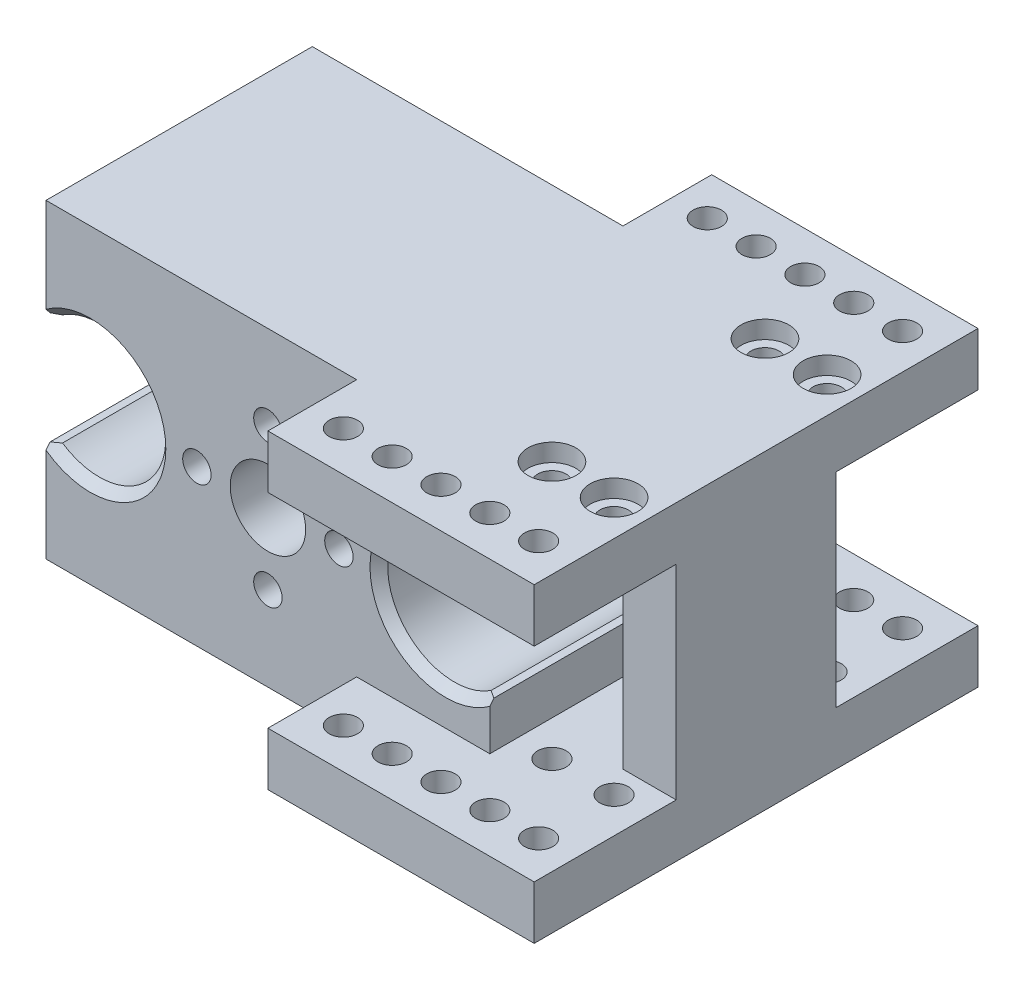
SolidWorks part; units mm, degrees
ref_plane "前视基准面" through (0, 0, 0) normal (0, 0, 1) x (1, 0, 0)
ref_plane "上视基准面" through (0, 0, 0) normal (0, 1, 0) x (1, 0, 0)
ref_plane "右视基准面" through (0, 0, 0) normal (1, 0, 0) x (0, 0, -1)
other "Configuration Table"
sketch "草图1" plane through (0, 0, 0) normal (0, 0, 1) x (1, 0, 0)
  line L1 (-25, -17.5) -> (25, -17.5)
  line L2 (-25, -17.5) -> (-25, 17.5)
  line L3 (-25, 17.5) -> (25, 17.5)
  line L4 (25, -17.5) -> (25, 17.5)
  line L5 (-25, -17.5) -> (25, 17.5) construction
  line L6 (-25, 17.5) -> (25, -17.5) construction
  point P0 (0, 0)
  dimension "D1" = 50
  dimension "D2" = 35
extrude "凸台-拉伸1" add sketch "草图1" along normal blind 30
hole_wizard "光轴孔" positions "草图2" profile "草图3" legacy end condition through all
sketch "草图2" plane through (0, 0, 30) normal (0, 0, 1) x (1, 0, 0)
  point P0 (0, 0)
sketch "草图3" plane through (0, 0, 30) normal (1, 0, 0) x (0, -1, 0)
  line L0 (0, 0) -> (0, 30)
  line L1 (0, 30) -> (4.25, 30)
  line L2 (4.25, 30) -> (4.25, 0)
  line L3 (4.25, 0) -> (0, 0)
  line L4 (0, 110) -> (0, -10) construction
  dimension "直径" = 8.5
  dimension "深度" = 30
hole_wizard "光轴座螺丝孔" positions "草图4" profile "草图5" legacy end condition through all
sketch "草图4" plane through (0, 0, 30) normal (0, 0, 1) x (1, 0, 0)
  point P0 (8, 0)
  point P4 (0, 8)
  point P6 (-8, 0)
  point P8 (0, -8)
  dimension "D1" = 8
  dimension "D2" = 8
  dimension "D3" = 8
  dimension "D4" = 8
sketch "草图5" plane through (8, 0, 30) normal (1, 0, 0) x (0, -1, 0)
  line L0 (0, 0) -> (0, 30)
  line L1 (0, 30) -> (1.6, 30)
  line L2 (1.6, 30) -> (1.6, 0)
  line L3 (1.6, 0) -> (0, 0)
  line L4 (0, 110) -> (0, -10) construction
  dimension "直径" = 3.2
  dimension "深度" = 30
hole_wizard "直线轴承座孔" positions "草图6" profile "草图7" legacy end condition through all
sketch "草图6" plane through (0, 0, 30) normal (0, 0, 1) x (1, 0, 0)
  point P0 (20, 0)
  point P2 (-20, 0)
  dimension "D1" = 20
  dimension "D2" = 20
sketch "草图7" plane through (20, 0, 30) normal (1, 0, 0) x (0, -1, 0)
  line L0 (0, 0) -> (0, 30)
  line L1 (0, 30) -> (7.5, 30)
  line L2 (7.5, 30) -> (7.5, 0)
  line L3 (7.5, 0) -> (0, 0)
  line L4 (0, 110) -> (0, -10) construction
  dimension "直径" = 15
  dimension "深度" = 30
chamfer "倒角1" distance 1 angle 45 8 edges at (25, -5.5902, 15) (12.5, 0, 30) (25, 5.5902, 15) (12.5, 0, 0) (-12.5, 0, 30) (-12.5, 0, 0) (-25, 5.5902, 15) (-25, -5.5902, 15) first distance on face at (18.75, 0, 15) first distance on face at (-18.75, 0, 15)
sketch "草图9" plane through (25, 0, 0) normal (1, 0, 0) x (0, 0, -1)
  line L0 (0, 6.8739) -> (0, 17.5) construction
  line L1 (-30, 17.5) -> (0, 17.5)
  line L2 (-30, 17.5) -> (-30, 11.5)
  line L3 (-30, 11.5) -> (0, 11.5)
  line L4 (0, 17.5) -> (0, 11.5)
  line L5 (-30, -17.5) -> (-30, -6.8739) construction
  line L6 (0, -17.5) -> (-30, -17.5)
  line L7 (0, -17.5) -> (0, -11.5)
  line L8 (0, -11.5) -> (-30, -11.5)
  line L9 (-30, -17.5) -> (-30, -11.5)
  dimension "D1" = 6
  dimension "D2" = 6
extrude "凸台-拉伸3" add sketch "草图9" along normal blind 15
ref_plane "基准面1" through (0, 0, 15) normal (0, 0, 1) x (1, 0, 0)
sketch "草图10" plane through (0, 0, 15) normal (0, 0, 1) x (1, 0, 0)
  line L6 (40, 11.5) -> (25, 11.5) construction
  line L7 (40, -11.5) -> (34, -11.5)
  line L8 (40, -11.5) -> (40, 11.5)
  line L9 (40, 11.5) -> (34, 11.5)
  line L10 (34, -11.5) -> (34, 11.5)
  dimension "D1" = 6
extrude "凸台-拉伸4" add sketch "草图10" along normal mid plane 18
hole_wizard "孔1" positions "草图11" profile "草图12" legacy end condition through all
sketch "草图11" plane through (0, 11.5, 0) normal (0, -1, 0) x (-1, 0, 0)
  line L0 (-40, 0) -> (-25, 0) construction
  line L3 (-40, -6) -> (-40, 0) construction
  line L4 (-25, -30) -> (-25, 0) construction
  point P0 (-36, -3)
  point P27 (-29, -3)
  dimension "D1" = 3
  dimension "D2" = 4
  dimension "D3" = 4
sketch "草图12" plane through (36, 11.5, 3) normal (1, 0, 0) x (0, 0, -1)
  line L0 (0, 0) -> (0, 6)
  line L1 (0, 6) -> (1.6, 6)
  line L2 (1.6, 6) -> (1.6, 0)
  line L3 (1.6, 0) -> (0, 0)
  line L4 (0, 110) -> (0, -10) construction
  dimension "直径" = 3.2
  dimension "深度" = 6
mirror "镜向1" about plane through (0, 0, 15) normal (0, 0, 1) of "孔1"
ref_plane "基准面2" through (0, 0, 0) normal (0, -1, 0) x (-1, 0, 0)
mirror "镜向2" about plane through (0, 0, 0) normal (0, -1, 0) of "镜向1", "孔1"
sketch "草图15" plane through (0, 0, 0) normal (0, 0, -1) x (-1, 0, 0)
  line L0 (-40, 17.5) -> (25, 17.5) construction
  line L1 (-40, 11.5) -> (-10, 11.5)
  line L2 (-40, 11.5) -> (-40, 17.5)
  line L3 (-40, 17.5) -> (-10, 17.5)
  line L4 (-10, 11.5) -> (-10, 17.5)
  dimension "D1" = 30
extrude "凸台-拉伸6" add sketch "草图15" along normal blind 10
hole_wizard "孔2" positions "草图16" profile "草图17" legacy end condition through all
sketch "草图16" plane through (0, 11.5, 0) normal (0, -1, 0) x (-1, 0, 0)
  line L0 (-40, 10) -> (-10, 10) construction
  line L1 (-10, 10) -> (-10, 0) construction
  line L4 (-14, 5.5) -> (-25, 5.5)
  line L5 (-25, 10) -> (-25, 0)
  line L6 (-10, 10) -> (-40, 10) construction
  point P6 (-19.5, 5.5)
  point P8 (-14, 5.5)
  point P10 (-25, 5.5)
  dimension "D1" = 4.5
  dimension "D2" = 4
sketch "草图17" plane through (19.5, 11.5, -5.5) normal (1, 0, 0) x (0, 0, -1)
  line L0 (0, 0) -> (0, 6)
  line L1 (0, 6) -> (1.6, 6)
  line L2 (1.6, 6) -> (1.6, 0)
  line L3 (1.6, 0) -> (0, 0)
  line L4 (0, 110) -> (0, -10) construction
  dimension "直径" = 3.2
  dimension "深度" = 6
ref_plane "基准面3" through (25, 0, 0) normal (1, 0, 0) x (0, 0, -1)
mirror "镜向4" about plane through (25, 0, 0) normal (1, 0, 0) of "孔2"
mirror "镜向5" about plane through (0, 0, 15) normal (0, 0, 1) of "镜向4", "孔2", "凸台-拉伸6"
mirror "镜向6" about plane through (0, 0, 0) normal (0, -1, 0) of "镜向5", "镜向4", "孔2", "凸台-拉伸6"
hole_wizard "孔3" positions "草图19" profile "草图20" legacy
sketch "草图19" plane through (0, -17.5, 0) normal (0, -1, 0) x (-1, 0, 0)
  point P0 (-29, -3)
  point P3 (-36, -3)
  point P6 (-36, -27)
  point P9 (-29, -27)
sketch "草图20" plane through (29, -17.5, 3) normal (1, 0, 0) x (0, 0, -1)
  line L0 (0, 0) -> (0, 2)
  line L1 (0, 2) -> (2.7, 2)
  line L2 (2.7, 2) -> (2.7, 0)
  line L3 (2.7, 0) -> (0, 0)
  line L4 (0, 110) -> (0, -10) construction
  dimension "直径" = 5.4
  dimension "深度" = 2
mirror "镜向7" about plane through (0, 0, 0) normal (0, -1, 0) of "孔3"
hole_wizard "孔4" positions "草图21" profile "草图22" legacy
sketch "草图21" plane through (0, 0, 0) normal (0, 0, -1) x (-1, 0, 0)
  point P0 (0, 0)
sketch "草图22" plane through (0, 0, 0) normal (1, 0, 0) x (0, 1, 0)
  line L0 (0, 0) -> (0, 12)
  line L1 (0, 12) -> (6, 12)
  line L2 (6, 12) -> (6, 0)
  line L3 (6, 0) -> (0, 0)
  line L4 (0, 110) -> (0, -10) construction
  dimension "直径" = 12
  dimension "深度" = 12
